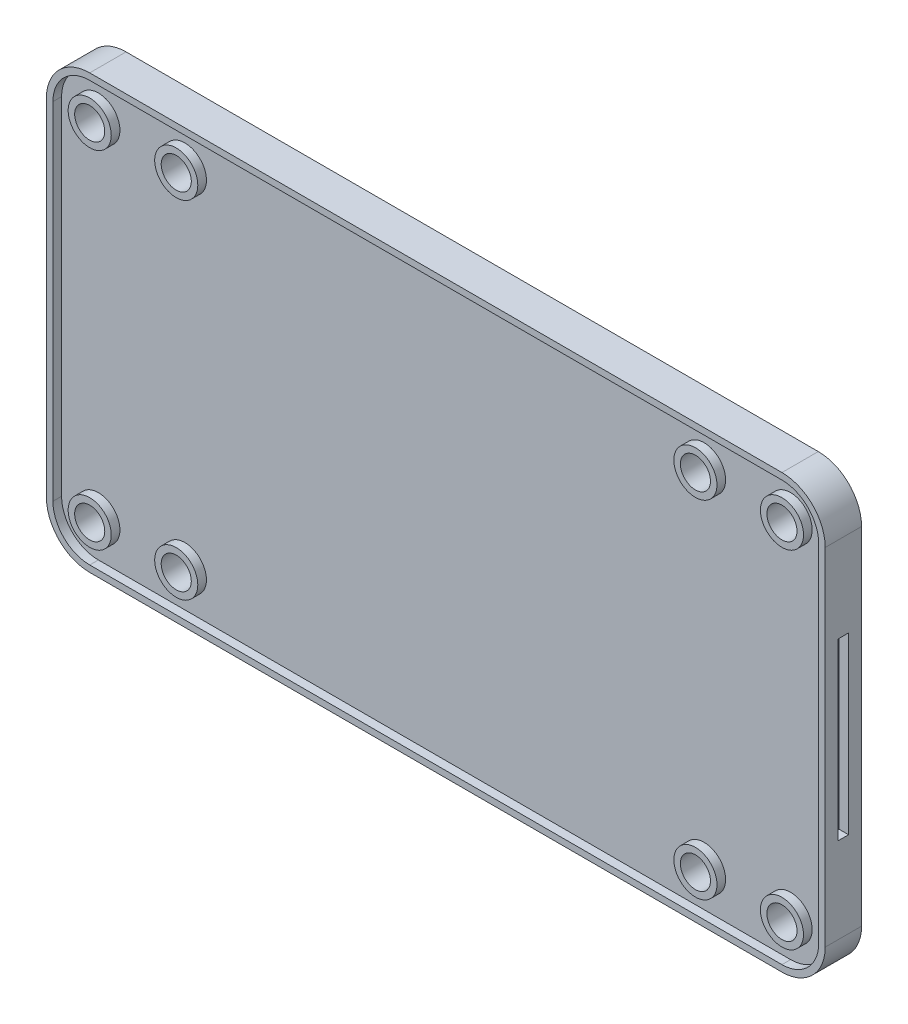
SolidWorks part; units mm, degrees
material "ABS"
ref_plane "Front Plane" through (0, 0, 0) normal (0, 0, 1) x (1, 0, 0)
ref_plane "Top Plane" through (0, 0, 0) normal (0, 1, 0) x (1, 0, 0)
ref_plane "Right Plane" through (0, 0, 0) normal (1, 0, 0) x (0, 0, -1)
sketch "Sketch1" plane through (0, 0, 0) normal (0, 0, 1) x (1, 0, 0)
  line L0 (-57.15, 0) -> (57.15, 0) construction
  line L1 (-50.8, -31.75) -> (50.8, -31.75)
  line L2 (-57.15, -25.4) -> (-57.15, 25.4)
  line L3 (-50.8, 31.75) -> (50.8, 31.75)
  line L4 (57.15, -25.4) -> (57.15, 25.4)
  line L5 (-57.15, -31.75) -> (57.15, 31.75) construction
  line L6 (-57.15, 31.75) -> (57.15, -31.75) construction
  line L7 (0, 31.75) -> (0, -31.75) construction
  arc A0 (50.8, 31.75) -> (57.15, 25.4) centre (50.8, 25.4) cw
  arc A1 (50.8, -31.75) -> (57.15, -25.4) centre (50.8, -25.4) ccw
  arc A2 (-50.8, -31.75) -> (-57.15, -25.4) centre (-50.8, -25.4) cw
  arc A3 (-57.15, 25.4) -> (-50.8, 31.75) centre (-50.8, 25.4) cw
  circle A4 centre (-50.8, -25.4) radius 2.2098
  circle A5 centre (-38.1, -25.4) radius 2.2098
  circle A6 centre (-50.8, 25.4) radius 2.2098
  circle A7 centre (-38.1, 25.4) radius 2.2098
  circle A8 centre (50.8, 25.4) radius 2.2098
  circle A9 centre (38.1, 25.4) radius 2.2098
  circle A10 centre (50.8, -25.4) radius 2.2098
  circle A11 centre (38.1, -25.4) radius 2.2098
  point P0 (0, 0)
  dimension "D3" = 6.35
  dimension "D4" = 4.4196
  dimension "D1" = 63.5
  dimension "D2" = 114.3
  dimension "D5" = 6.35
  dimension "D6" = 12.7
  dimension "D7" = 6.35
extrude "Boss-Extrude1" add sketch "Sketch1" against normal blind 3.175
sketch "Sketch2" plane through (0, 0, 0) normal (0, 0, 1) x (1, 0, 0)
  line L12 (50.8, 30.7975) -> (-50.8, 30.7975)
  line L13 (-56.1975, 25.4) -> (-56.1975, -25.4)
  line L14 (-50.8, -30.7975) -> (50.8, -30.7975)
  line L15 (56.1975, -25.4) -> (56.1975, 25.4)
  line L16 (50.8, 30.7975) -> (-50.8, 30.7975)
  line L17 (-56.1975, 25.4) -> (-56.1975, -25.4)
  line L18 (-50.8, -30.7975) -> (50.8, -30.7975)
  line L19 (56.1975, -25.4) -> (56.1975, 25.4)
  circle A0 centre (-50.8, -25.4) radius 2.2098 construction
  arc A8 (56.1975, 25.4) -> (50.8, 30.7975) centre (50.8, 25.4) ccw
  arc A9 (-50.8, 30.7975) -> (-56.1975, 25.4) centre (-50.8, 25.4) ccw
  arc A10 (-56.1975, -25.4) -> (-50.8, -30.7975) centre (-50.8, -25.4) ccw
  arc A11 (50.8, -30.7975) -> (56.1975, -25.4) centre (50.8, -25.4) ccw
  arc A12 (56.1975, 25.4) -> (50.8, 30.7975) centre (50.8, 25.4) ccw
  arc A13 (-50.8, 30.7975) -> (-56.1975, 25.4) centre (-50.8, 25.4) ccw
  arc A14 (-56.1975, -25.4) -> (-50.8, -30.7975) centre (-50.8, -25.4) ccw
  arc A15 (50.8, -30.7975) -> (56.1975, -25.4) centre (50.8, -25.4) ccw
  circle A36 centre (38.1, 25.4) radius 3.1623
  circle A37 centre (50.8, 25.4) radius 3.1623
  circle A38 centre (50.8, -25.4) radius 3.1623
  circle A39 centre (38.1, -25.4) radius 3.1623
  circle A40 centre (-38.1, -25.4) radius 3.1623
  circle A41 centre (-50.8, -25.4) radius 3.1623
  circle A42 centre (-38.1, 25.4) radius 3.1623
  circle A43 centre (-50.8, 25.4) radius 3.1623
  circle A44 centre (-38.1, -25.4) radius 2.2098 construction
  circle A47 centre (38.1, -25.4) radius 2.2098 construction
  circle A50 centre (50.8, -25.4) radius 2.2098 construction
  circle A51 centre (50.8, 25.4) radius 2.2098 construction
  circle A52 centre (38.1, 25.4) radius 2.2098 construction
  circle A53 centre (-38.1, 25.4) radius 2.2098 construction
  circle A54 centre (-50.8, 25.4) radius 2.2098 construction
  dimension "D2" = 0.9525
  dimension "D1" = 0.9525
extrude "Cut-Extrude3" cut sketch "Sketch2" against normal blind 1.27
sketch "Sketch3" plane through (0, 0, -3.175) normal (0, 0, -1) x (-1, 0, 0)
  line L4 (-57.15, 25.4) -> (-57.15, -25.4)
  line L5 (-50.8, -31.75) -> (50.8, -31.75)
  line L6 (57.15, -25.4) -> (57.15, 25.4)
  line L7 (50.8, 31.75) -> (-50.8, 31.75)
  line L8 (-57.15, 25.4) -> (-57.15, -25.4)
  line L9 (-50.8, -31.75) -> (50.8, -31.75)
  line L10 (57.15, -25.4) -> (57.15, 25.4)
  line L11 (50.8, 31.75) -> (-50.8, 31.75)
  circle A0 centre (-50.8, -25.4) radius 2.2098 construction
  circle A1 centre (-38.1, -25.4) radius 2.2098 construction
  circle A2 centre (38.1, -25.4) radius 2.2098 construction
  circle A3 centre (50.8, -25.4) radius 2.2098 construction
  arc A4 (-50.8, 31.75) -> (-57.15, 25.4) centre (-50.8, 25.4) ccw
  arc A5 (-57.15, -25.4) -> (-50.8, -31.75) centre (-50.8, -25.4) ccw
  arc A6 (50.8, -31.75) -> (57.15, -25.4) centre (50.8, -25.4) ccw
  arc A7 (57.15, 25.4) -> (50.8, 31.75) centre (50.8, 25.4) ccw
  arc A8 (-50.8, 31.75) -> (-57.15, 25.4) centre (-50.8, 25.4) ccw
  arc A9 (-57.15, -25.4) -> (-50.8, -31.75) centre (-50.8, -25.4) ccw
  arc A10 (50.8, -31.75) -> (57.15, -25.4) centre (50.8, -25.4) ccw
  arc A11 (57.15, 25.4) -> (50.8, 31.75) centre (50.8, 25.4) ccw
  circle A12 centre (50.8, 25.4) radius 2.2098 construction
  circle A13 centre (38.1, 25.4) radius 2.2098 construction
  circle A14 centre (-38.1, 25.4) radius 2.2098 construction
  circle A15 centre (-50.8, 25.4) radius 2.2098 construction
  circle A16 centre (-50.8, -25.4) radius 2.2098
  circle A17 centre (-38.1, -25.4) radius 2.2098
  circle A18 centre (38.1, -25.4) radius 2.2098
  circle A19 centre (50.8, -25.4) radius 2.2098
  circle A20 centre (50.8, 25.4) radius 2.2098
  circle A21 centre (38.1, 25.4) radius 2.2098
  circle A22 centre (-38.1, 25.4) radius 2.2098
  circle A23 centre (-50.8, 25.4) radius 2.2098
  dimension "D1" = 0
extrude "Boss-Extrude2" add sketch "Sketch3" along normal blind 2.159
sketch "Sketch4" plane through (57.15, 0, 0) normal (1, 0, 0) x (0, 0, -1)
  line L0 (5.334, -25.4) -> (0, -25.4) construction
  line L1 (1.905, 12.827) -> (3.429, 12.827)
  line L2 (1.905, 12.827) -> (1.905, -12.827)
  line L3 (1.905, -12.827) -> (3.429, -12.827)
  line L4 (3.429, 12.827) -> (3.429, -12.827)
  point P6 (2.667, -25.4)
  point P7 (2.667, -12.827)
  point P8 (1.905, 0)
  dimension "D1" = 1.524
  dimension "D2" = 25.654
extrude "Cut-Extrude4" cut sketch "Sketch4" against normal blind 1.397
mirror "Mirror1" about plane through (0, 0, 0) normal (1, 0, 0) of "Cut-Extrude4"
equation "\"tolerance\"= 0.005"
equation "\"D4@Sketch1\"=0.164 + \"tolerance\" * 2"
equation "\"D1@Boss-Extrude2\"= 0.080000in + \"tolerance\""
equation "\"D1@Sketch4\" = 0.05 + \"tolerance\" * 2"
equation "\"D2@Sketch4\" = 1 + \"tolerance\" * 2"
equation "\"D1@Cut-Extrude4\"= 0.05 + \"tolerance\""
